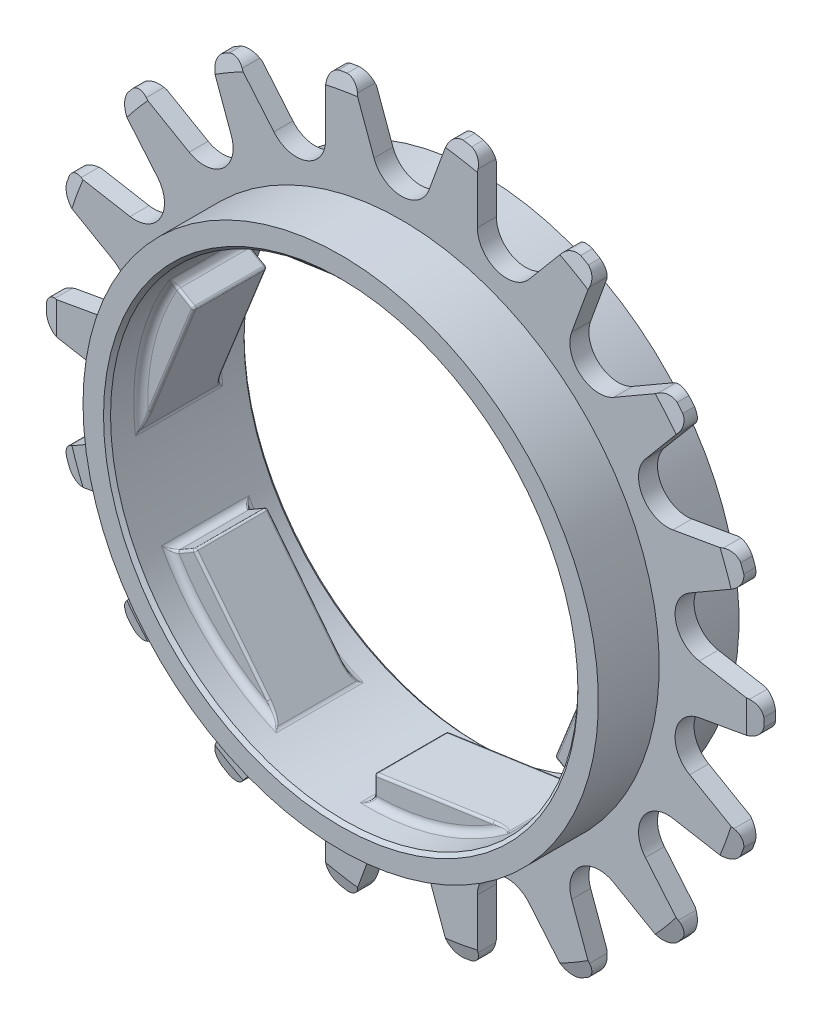
SolidWorks part; units mm, degrees
material "Chrome Stainless Steel"
ref_plane "Front" through (0, 0, 0) normal (0, 0, 1) x (1, 0, 0)
ref_plane "Top" through (0, 0, 0) normal (0, 1, 0) x (1, 0, 0)
ref_plane "Right" through (0, 0, 0) normal (1, 0, 0) x (0, 0, -1)
sketch "Sketch1" plane through (0, 0, 0) normal (0, 0, 1) x (1, 0, 0)
  circle A0 centre (0, 0) radius 38.8938
  dimension "D1" = 77.7875
extrude "Boss-Extrude1" add sketch "Sketch1" along normal mid plane 2.0574
sketch "Sketch2" plane through (0, 0, 0) normal (1, 0, 0) x (0, 0, -1)
  line L0 (-1.3156, 36.3538) -> (-0.635, 38.8937)
  line L1 (-0.635, 38.8937) -> (0.635, 38.8937)
  line L2 (0.635, 38.8937) -> (1.3156, 36.3538)
  line L3 (1.3156, 36.3538) -> (2.54, 36.3537)
  line L4 (2.54, 36.3537) -> (2.54, 41.4337)
  line L5 (2.54, 41.4337) -> (-2.54, 41.4337)
  line L6 (-1.3156, 36.3538) -> (-2.54, 36.3537)
  line L7 (0, 0) -> (-38.8938, 0) construction
  line L8 (-2.54, 36.3537) -> (-2.54, 41.4337)
  line L9 (0, 38.8937) -> (0, 0) construction
  dimension "D1" = 77.7875
  dimension "D2" = 1.27
  dimension "D3" = 30
  dimension "D4" = 2.54
  dimension "D5" = 5.08
  dimension "D6" = 5.08
revolve "Cut-Revolve1" cut sketch "Sketch2" angle 360 about L7
sketch "Sketch3" plane through (0, 0, 0) normal (0, 0, 1) x (1, 0, 0)
  line L0 (0, 0) -> (0, 40.923) construction
  line L1 (-6.2823, 40.923) -> (0, 0) construction
  line L2 (0, 0) -> (6.2823, 40.923) construction
  line L3 (-4.8502, 37.3803) -> (-2.9835, 32.2516)
  line L4 (4.8502, 37.3803) -> (2.9835, 32.2516)
  line L5 (-6.2823, 38.383) -> (-6.2823, 40.923)
  line L6 (6.2823, 38.383) -> (6.2823, 40.923)
  line L7 (-6.2823, 40.923) -> (0, 40.923)
  line L8 (6.2823, 40.923) -> (0, 40.923)
  arc A0 (-2.9835, 32.2516) -> (2.9835, 32.2516) centre (0, 33.3375) ccw
  arc A1 (-4.8502, 37.3803) -> (-6.2823, 38.383) centre (-6.2823, 36.859) ccw
  arc A2 (4.8502, 37.3803) -> (6.2823, 38.383) centre (6.2823, 36.859) cw
  circle A3 centre (-6.2823, 36.859) radius 1.524 construction
  circle A4 centre (6.2823, 36.859) radius 1.524 construction
  circle A5 centre (0, 0) radius 38.8938 construction
  circle A6 centre (0, 0) radius 30.1625 construction
  dimension "D1" = 3.175
  dimension "D4" = 1.524
  dimension "D5" = 77.7875
  dimension "D6" = 60.325
  dimension "D2" = 2.54
  dimension "D3" = 40
extrude "Cut-Extrude2" cut sketch "Sketch3" against normal through all both and the other way through all
pattern_circular "CirPattern1" count 18 over 360 about axis through (0, 0, 0) along (0, 0, 1) of "Cut-Extrude2"
sketch "Sketch4" plane through (0, 0, 0) normal (0, 0, 1) x (1, 0, 0)
  circle A0 centre (0, 0) radius 27.94
  dimension "D1" = 55.88
extrude "Boss-Extrude2" add sketch "Sketch4" along normal mid plane 15.24
sketch "Sketch5" plane through (0, 0, 0) normal (0, 0, -1) x (-1, 0, 0)
  circle A0 centre (0, 0) radius 25.3365
  dimension "D1" = 50.673
extrude "Cut-Extrude3" cut sketch "Sketch5" against normal through all both and the other way through all
chamfer "Chamfer1" distance 0.381 angle 45 2 edges at (-25.3365, 0, -7.62) (-25.3365, 0, 7.62)
sketch "Sketch6" plane through (0, 0, 0) normal (0, 0, 1) x (1, 0, 0)
  line L0 (0, 25.7175) -> (0, 22.5425)
  line L1 (0, 22.5425) -> (-15.875, 20.233)
  circle A0 centre (0, 0) radius 25.7175 construction
  arc A1 (-15.875, 20.233) -> (0, 25.7175) centre (-0.1317, 0.3813) cw
  dimension "D1" = 3.175
  dimension "D3" = 25.3365
  dimension "D2" = 15.875
extrude "Boss-Extrude4" add sketch "Sketch6" along normal mid plane 7.9375
fillet "Fillet1" radius 0.762 4 edges at (0, 25.3365, 0) (-7.9513, 24.0565, -3.9687) (-15.0991, 20.3459, 0) (-7.9513, 24.0565, 3.9688)
fillet "Fillet2" radius 0.254 13 edges at (-15.173, 20.2829, 4.6325) (-14.3842, 20.4499, 4.1) (-15.173, 20.2829, -4.6325) (-14.5785, 20.4216, -4.1708) (0.1048, 24.9483, 4.0669) (0, 24.5686, 3.9688) (0.1048, 24.9483, -4.0669) (0, 24.5686, -3.9688) (-6.7065, 21.5668, 3.9688) (0, 22.5425, 0) (-6.7065, 21.5668, -3.9688) (0, 23.5526, 3.9688) (0, 23.5526, -3.9688)
pattern_circular "CirPattern2" count 6 over 360 about axis through (0, 0, 7.62) along (0, 0, -1) of "Boss-Extrude4", "Fillet1", "Fillet2"
equation "\"DiameterSprocket\"= 3.0625"
equation "\"ThicknessSprocket\"= .081"
equation "\"D1@Sketch1\"=\"DiameterSprocket\""
equation "\"D1@Boss-Extrude1\"=\"ThicknessSprocket\""
equation "\"D1@Sketch2\"=\"DiameterSprocket\""
equation "\"thicknessFlat\"= .05"
equation "\"angleCombined\"= 30deg"
equation "\"D2@Sketch2\"=\"thicknessFlat\""
equation "\"D3@Sketch2\"=\"angleCombined\""
equation "\"D4@Sketch2\"=\"thicknessFlat\"*2"
equation "\"tooth_rad_bttm\"= .125"
equation "\"D1@Sketch3\"=\"tooth_rad_bttm\""
equation "\"D5@Sketch3\"=\"DiameterSprocket\""
equation "\"toothAngle\"= 40deg"
equation "\"D3@Sketch3\"=\"toothAngle\""
equation "\"toothRadTop\"= .06"
equation "\"D4@Sketch3\"=\"toothRadTop\""
equation "\"toothDistBetweenTeeth\"= 31 / 64"
equation "\"thicknessBody\"= .6"
equation "\"diameterMainBody\"= 2.2"
equation "\"D1@Sketch4\"=\"diameterMainBody\""
equation "\"D1@Boss-Extrude2\"=\"thicknessBody\""
equation "\"diameterInsideDetail\"= 1.995"
equation "\"D1@Sketch5\"=\"diameterInsideDetail\""
equation "\"D3@Sketch6\"=\"diameterInsideDetail\"/2"
